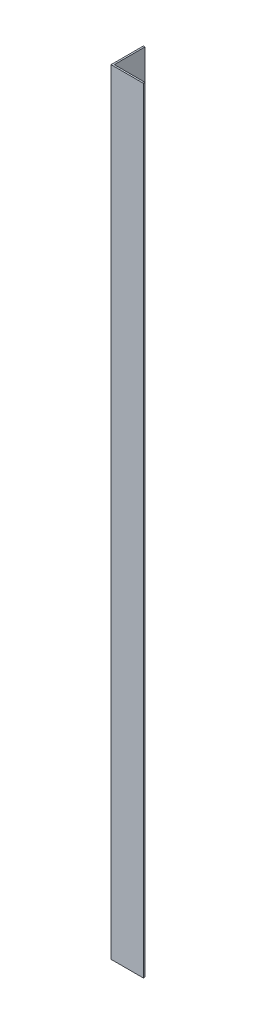
SolidWorks part; units mm, degrees
material "1060 Сплав"
ref_plane "Спереди" through (0, 0, 0) normal (0, 0, 1) x (1, 0, 0)
ref_plane "Сверху" through (0, 0, 0) normal (0, 1, 0) x (1, 0, 0)
ref_plane "Справа" through (0, 0, 0) normal (1, 0, 0) x (0, 0, -1)
sketch "Эскиз1" plane through (0, 0, 0) normal (0, 1, 0) x (1, 0, 0)
  line L0 (0, 0) -> (0, 15)
  line L1 (0, 15) -> (0.75, 15)
  line L2 (0.75, 15) -> (0.75, 0.75)
  line L3 (0.75, 0.75) -> (15, 0.75)
  line L4 (15, 0.75) -> (15, 0)
  line L5 (15, 0) -> (0, 0)
  dimension "D1" = 0.75
  dimension "D2" = 15
extrude "Бобышка-Вытянуть1" add sketch "Эскиз1" along normal blind 360
